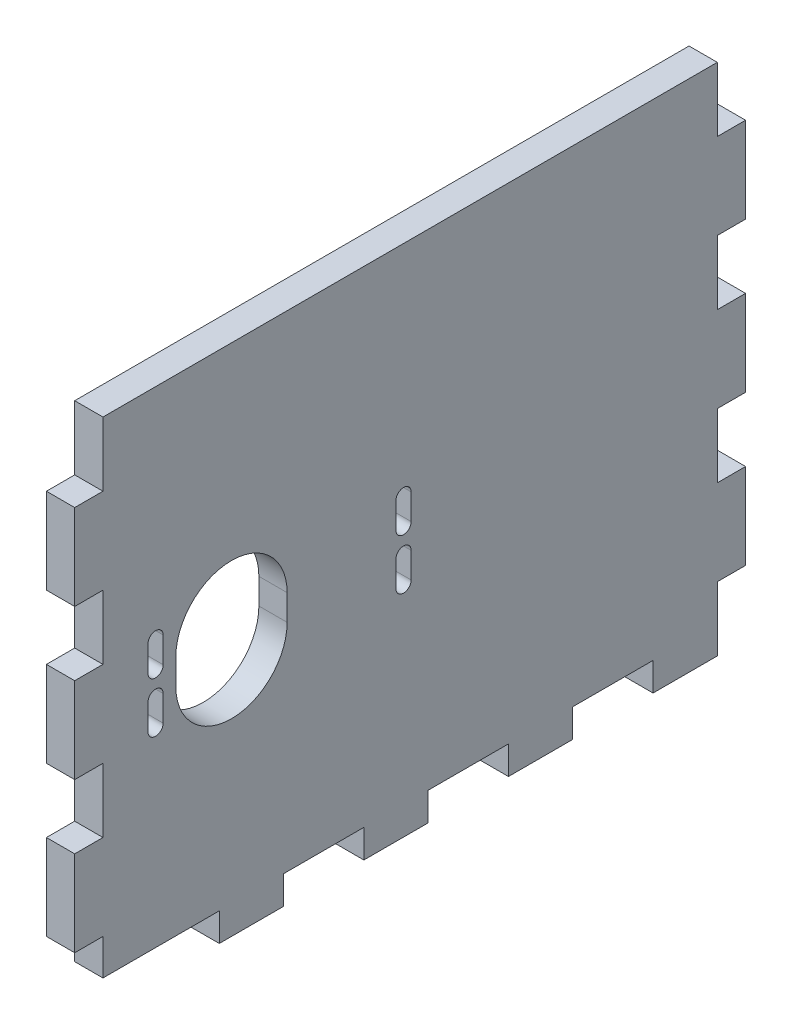
SolidWorks part; units mm, degrees
material "Acrylic (Medium-high impact)"
ref_plane "Front" through (0, 0, 0) normal (0, 0, 1) x (1, 0, 0)
ref_plane "Top" through (0, 0, 0) normal (0, 1, 0) x (1, 0, 0)
ref_plane "Right" through (0, 0, 0) normal (1, 0, 0) x (0, 0, -1)
sketch "Sketch1" plane through (0, 0, 0) normal (0, 0, 1) x (1, 0, 0)
  line L0 (0, 143.002) -> (0, -143.002) construction
  line L1 (-3.302, 133.858) -> (-3.302, -143.002)
  line L2 (-3.302, -143.002) -> (3.302, -143.002)
  line L3 (3.302, 143.002) -> (3.302, -143.002)
  line L4 (3.302, 143.002) -> (-16.256, 143.002)
  line L5 (-5.842, 136.398) -> (-16.256, 136.398)
  line L6 (-16.256, 143.002) -> (-16.256, 136.398)
  line L8 (-28.956, 155.448) -> (16.002, 155.448)
  line L9 (-28.956, 155.448) -> (-28.956, -149.352)
  line L10 (-28.956, -149.352) -> (16.002, -149.352)
  line L11 (16.002, 155.448) -> (16.002, -149.352)
  arc A0 (-3.302, 133.858) -> (-5.842, 136.398) centre (-5.842, 133.858) ccw
  point P2 (0, -143.002)
  point P11 (0, 0)
  dimension "D5" = 2.54
  dimension "D1" = 6.604
  dimension "D2" = 12.954
  dimension "D3" = 6.604
  dimension "D4" = 286.004
  dimension "D6" = 304.8
  dimension "D7" = 6.35
  dimension "D8" = 12.7
  dimension "D9" = 12.7
extrude "Boss-Extrude1" add sketch "Sketch1" along normal blind 5.588
sketch "Sketch2" plane through (16.002, 0, 0) normal (1, 0, 0) x (0, 0, -1)
  line L0 (-5.588, -149.352) -> (-5.588, 155.448) construction
  line L1 (-5.588, -47.752) -> (127, -47.752)
  line L2 (-5.588, -47.752) -> (-5.588, -149.352)
  line L3 (-5.588, -149.352) -> (127, -149.352)
  line L4 (127, -47.752) -> (127, -149.352)
  line L5 (14.4, -101.092) -> (14.4, -96.012)
  line L6 (36.4, -96.012) -> (36.4, -101.092)
  line L7 (8.4, -116.592) -> (8.4, -111.512)
  line L8 (11.4, -116.592) -> (11.4, -111.512)
  line L9 (8.4, -85.592) -> (8.4, -80.512)
  line L10 (11.4, -85.592) -> (11.4, -80.512)
  line L11 (25.4, -96.012) -> (25.4, -101.092) construction
  line L12 (42.4, -116.592) -> (42.4, -111.512)
  line L13 (39.4, -116.592) -> (39.4, -111.512)
  line L14 (39.4, -85.592) -> (39.4, -80.512)
  line L15 (42.4, -85.592) -> (42.4, -80.512)
  line L16 (0, -149.352) -> (0, 155.448) construction
  line L17 (124.206, -60.452) -> (124.206, -77.3853) construction
  line L18 (127, -47.752) -> (121.412, -47.752)
  line L19 (127, -47.752) -> (127, -60.452)
  line L20 (127, -60.452) -> (121.412, -60.452)
  line L21 (121.412, -47.752) -> (121.412, -60.452)
  line L22 (127, -107.0187) -> (121.412, -107.0187)
  line L23 (127, -107.0187) -> (127, -119.7187)
  line L24 (127, -119.7187) -> (121.412, -119.7187)
  line L25 (121.412, -107.0187) -> (121.412, -119.7187)
  line L26 (127, -136.652) -> (121.412, -136.652)
  line L27 (127, -136.652) -> (127, -149.352)
  line L28 (127, -149.352) -> (121.412, -149.352)
  line L29 (121.412, -136.652) -> (121.412, -149.352)
  line L30 (127, -77.3853) -> (121.412, -77.3853)
  line L31 (127, -77.3853) -> (127, -90.0853)
  line L32 (127, -90.0853) -> (121.412, -90.0853)
  line L33 (121.412, -77.3853) -> (121.412, -90.0853)
  line L34 (124.206, -90.0853) -> (124.206, -107.0187) construction
  line L35 (124.206, -119.7187) -> (124.206, -136.652) construction
  line L36 (10.4, -93.552) -> (59.4, -93.552) construction
  line L37 (59.4, -93.552) -> (59.4, -103.552) construction
  line L38 (59.4, -103.552) -> (10.4, -103.552) construction
  line L39 (10.4, -103.552) -> (10.4, -93.552) construction
  line L40 (8.9, -93.552) -> (8.9, -96.092)
  line L41 (11.9, -96.092) -> (11.9, -93.552)
  line L42 (11.9, -93.552) -> (11.9, -91.012)
  line L43 (8.9, -91.012) -> (8.9, -93.552)
  line L44 (8.9, -106.092) -> (8.9, -101.012)
  line L45 (11.9, -101.012) -> (11.9, -106.092)
  line L46 (60.9, -91.012) -> (60.9, -96.092)
  line L47 (57.9, -96.092) -> (57.9, -91.012)
  line L48 (60.9, -106.092) -> (60.9, -101.012)
  line L49 (57.9, -101.012) -> (57.9, -106.092)
  arc A0 (14.4, -101.092) -> (36.4, -101.092) centre (25.4, -101.092) ccw
  arc A1 (36.4, -96.012) -> (14.4, -96.012) centre (25.4, -96.012) ccw
  arc A2 (8.4, -116.592) -> (11.4, -116.592) centre (9.9, -116.592) ccw
  arc A3 (11.4, -111.512) -> (8.4, -111.512) centre (9.9, -111.512) ccw
  arc A4 (8.4, -85.592) -> (11.4, -85.592) centre (9.9, -85.592) ccw
  arc A5 (11.4, -80.512) -> (8.4, -80.512) centre (9.9, -80.512) ccw
  arc A6 (42.4, -116.592) -> (39.4, -116.592) centre (40.9, -116.592) cw
  arc A7 (39.4, -111.512) -> (42.4, -111.512) centre (40.9, -111.512) cw
  arc A8 (42.4, -85.592) -> (39.4, -85.592) centre (40.9, -85.592) cw
  arc A9 (39.4, -80.512) -> (42.4, -80.512) centre (40.9, -80.512) cw
  circle A10 centre (10.4, -93.552) radius 1.5
  circle A11 centre (59.4, -93.552) radius 1.5
  circle A12 centre (10.4, -103.552) radius 1.5
  circle A13 centre (59.4, -103.552) radius 1.5
  arc A14 (8.9, -96.092) -> (11.9, -96.092) centre (10.4, -96.092) ccw
  arc A15 (11.9, -91.012) -> (8.9, -91.012) centre (10.4, -91.012) ccw
  arc A16 (8.9, -101.012) -> (11.9, -101.012) centre (10.4, -101.012) cw
  arc A17 (11.9, -106.092) -> (8.9, -106.092) centre (10.4, -106.092) cw
  arc A18 (60.9, -96.092) -> (57.9, -96.092) centre (59.4, -96.092) cw
  arc A19 (57.9, -91.012) -> (60.9, -91.012) centre (59.4, -91.012) cw
  arc A20 (60.9, -101.012) -> (57.9, -101.012) centre (59.4, -101.012) ccw
  arc A21 (57.9, -106.092) -> (60.9, -106.092) centre (59.4, -106.092) ccw
  point P44 (25.4, -98.552)
  point P47 (-5.588, -98.552)
  point P71 (10.4, -98.552)
  point P72 (14.4, -98.552)
  point P103 (60.9, -93.552)
  point P105 (60.9, -103.552)
  point P106 (11.9, -103.552)
  line M17 (0, -149.352) -> (0, 155.448)
  line M19 (-5.588, 155.448) -> (-5.588, -149.352)
  line M20 (-5.588, -149.352) -> (0, -149.352)
  dimension "D1" = 22
  dimension "D6" = 1.5
  dimension "D10" = 1.5
  dimension "D18" = 3
  dimension "D2" = 5.08
  dimension "D3" = 5.08
  dimension "D4" = 15.5
  dimension "D5" = 15.5
  dimension "D7" = 15.5
  dimension "D8" = 15.5
  dimension "D9" = 5.08
  dimension "D11" = 25.4
  dimension "D12" = 50.8
  dimension "D13" = 101.6
  dimension "D14" = 12.7
  dimension "D15" = 5.588
  dimension "D16" = 10
  dimension "D17" = 49
  dimension "D19" = 5.08
  dimension "D20" = 5.08
  dimension "D21" = 15
extrude "Boss-Extrude2" add sketch "Sketch2" against normal blind 5.588 contours L33 L30 L4 L20 L21 L1 L3 L29 L26 L24 L25 L22 L32 A5 L10 A4 L9 A3 L8 A2 L7 A1 L6 A0 L5 L13 A7 L12 A6 L14 A9 L15 A8 M17 | L1 M19 M20 M17 | L10 A5 L9 A4 | A9 L14 A8 L15 | A7 L13 A6 L12 | L8 A3 L7 A2 region at (16.002, -98.552, -64.1244) region at (16.002, -98.552, 2.794) region at (16.002, -114.052, -9.9) region at (16.002, -83.052, -9.9) region at (16.002, -114.052, -40.9) region at (16.002, -83.052, -40.9)
sketch "Sketch3" plane through (10.414, 0, 0) normal (-1, 0, 0) x (0, 0, 1)
  line L0 (-121.412, -136.652) -> (-121.412, -149.352) construction
  line L1 (-121.412, -143.764) -> (0, -143.764)
  line L2 (-121.412, -143.764) -> (-121.412, -149.352)
  line L3 (-121.412, -149.352) -> (0, -149.352)
  line L4 (0, -143.764) -> (0, -149.352)
  dimension "D1" = 5.588
extrude "Boss-Extrude3" add sketch "Sketch3" along normal up to surface (39.37 mm away) up to face at (-28.956, 3.048, 2.794)
sketch "Sketch4" plane through (0, -149.352, 0) normal (0, -1, 0) x (1, 0, 0)
  line L0 (9.652, -22.987) -> (9.652, -35.687)
  line L1 (16.002, 5.588) -> (9.652, 5.588)
  line L2 (16.002, 5.588) -> (16.002, -7.112)
  line L3 (16.002, -7.112) -> (9.652, -7.112)
  line L4 (9.652, 5.588) -> (9.652, -7.112)
  line L5 (16.002, -22.987) -> (9.652, -22.987)
  line L6 (16.002, -22.987) -> (16.002, -35.687)
  line L7 (16.002, -35.687) -> (9.652, -35.687)
  line L8 (9.652, -51.562) -> (9.652, -64.262)
  line L9 (16.002, -51.562) -> (9.652, -51.562)
  line L10 (16.002, -51.562) -> (16.002, -64.262)
  line L11 (16.002, -64.262) -> (9.652, -64.262)
  line L12 (9.652, -80.137) -> (9.652, -92.837)
  line L13 (16.002, -80.137) -> (9.652, -80.137)
  line L14 (16.002, -80.137) -> (16.002, -92.837)
  line L15 (16.002, -92.837) -> (9.652, -92.837)
  line L16 (9.652, -108.712) -> (9.652, -121.412)
  line L17 (16.002, -108.712) -> (9.652, -108.712)
  line L18 (16.002, -108.712) -> (16.002, -121.412)
  line L19 (16.002, -121.412) -> (9.652, -121.412)
  line L36 (-6.477, 5.588) -> (-6.477, -121.412) construction
  line L37 (-28.956, 5.588) -> (16.002, 5.588) construction
  line L38 (-28.956, -121.412) -> (16.002, -121.412) construction
  line L39 (-22.606, 5.588) -> (-22.606, -121.412)
  line L40 (16.002, 5.588) -> (9.652, 5.588)
  line L41 (16.002, 5.588) -> (16.002, -121.412)
  line L42 (16.002, -121.412) -> (9.652, -121.412)
  line L43 (9.652, 5.588) -> (9.652, -121.412)
  line L44 (-28.956, -121.412) -> (-22.606, -121.412)
  line L45 (-28.956, 5.588) -> (-28.956, -121.412)
  line L46 (-28.956, 5.588) -> (-22.606, 5.588)
  line L47 (-28.956, -121.412) -> (-22.606, -121.412)
  line L48 (-28.956, -107.95) -> (-28.956, -121.412)
  line L49 (-28.956, -107.95) -> (-22.606, -107.95)
  line L50 (-22.606, -107.95) -> (-22.606, -121.412)
  line L51 (-28.956, -106.3625) -> (-22.606, -106.3625)
  line L52 (-28.956, -93.6625) -> (-28.956, -106.3625)
  line L53 (-28.956, -93.6625) -> (-22.606, -93.6625)
  line L54 (-22.606, -93.6625) -> (-22.606, -106.3625)
  line L55 (-28.956, -92.075) -> (-22.606, -92.075)
  line L56 (-28.956, -79.375) -> (-28.956, -92.075)
  line L57 (-28.956, -79.375) -> (-22.606, -79.375)
  line L58 (-22.606, -79.375) -> (-22.606, -92.075)
  line L59 (-28.956, -77.7875) -> (-22.606, -77.7875)
  line L60 (-28.956, -65.0875) -> (-28.956, -77.7875)
  line L61 (-28.956, -65.0875) -> (-22.606, -65.0875)
  line L62 (-22.606, -65.0875) -> (-22.606, -77.7875)
  line L63 (-28.956, -121.412) -> (-22.606, -121.412)
  line L64 (-28.956, -108.712) -> (-28.956, -121.412)
  line L65 (-28.956, -108.712) -> (-22.606, -108.712)
  line L66 (-22.606, -108.712) -> (-22.606, -121.412)
  line L67 (-28.956, -92.837) -> (-22.606, -92.837)
  line L68 (-28.956, -80.137) -> (-28.956, -92.837)
  line L69 (-28.956, -80.137) -> (-22.606, -80.137)
  line L70 (-22.606, -80.137) -> (-22.606, -92.837)
  line L71 (-28.956, -64.262) -> (-22.606, -64.262)
  line L72 (-28.956, -51.562) -> (-28.956, -64.262)
  line L73 (-28.956, -51.562) -> (-22.606, -51.562)
  line L74 (-22.606, -51.562) -> (-22.606, -64.262)
  line L75 (-28.956, -35.687) -> (-22.606, -35.687)
  line L76 (-28.956, -22.987) -> (-28.956, -35.687)
  line L77 (-28.956, -22.987) -> (-22.606, -22.987)
  line L78 (-22.606, 5.588) -> (-22.606, -7.112)
  line L79 (-28.956, -7.112) -> (-22.606, -7.112)
  line L80 (-28.956, 5.588) -> (-28.956, -7.112)
  line L81 (-28.956, 5.588) -> (-22.606, 5.588)
  line L82 (-22.606, -22.987) -> (-22.606, -35.687)
  line L83 (-16.129, 2.794) -> (-22.606, 2.794) construction
  line L85 (-28.956, 5.588) -> (-22.606, 5.588)
  line L86 (-28.956, 5.588) -> (-28.956, 0)
  line L87 (-28.956, 0) -> (-22.606, 0)
  line L88 (-22.606, 5.588) -> (-22.606, 0)
  line L92 (9.652, 5.588) -> (9.652, 0)
  line L93 (9.652, 5.588) -> (16.002, 5.588)
  line L94 (16.002, 5.588) -> (16.002, 0)
  line L95 (9.652, 0) -> (16.002, 0)
  line L96 (-28.956, 5.588) -> (16.002, 5.588)
  line L97 (-28.956, 5.588) -> (-28.956, 0)
  line L98 (-28.956, 0) -> (16.002, 0)
  line L99 (16.002, 5.588) -> (16.002, 0)
  line L100 (-9.652, 5.588) -> (-9.652, 0)
  line L101 (-9.652, 0) -> (-3.302, 0)
  line L102 (-3.302, 5.588) -> (-3.302, 0)
  line L103 (-9.652, 5.588) -> (-3.302, 5.588)
  line L104 (-9.779, 0) -> (-16.129, 0)
  line L105 (-9.779, 0) -> (-9.779, 5.588)
  line L106 (-9.779, 5.588) -> (-16.129, 5.588)
  line L107 (-16.129, 0) -> (-16.129, 5.588)
  line L108 (-9.779, 2.794) -> (-3.302, 2.794) construction
  line L109 (-3.302, 5.588) -> (-3.302, 0) construction
  line L111 (-28.956, 5.588) -> (16.002, 5.588)
  line L112 (-28.956, 5.588) -> (-28.956, 0)
  line L113 (-28.956, 0) -> (16.002, 0)
  line L114 (16.002, 5.588) -> (16.002, 0)
  line M38 (16.002, -121.412) -> (16.002, 5.588)
  line M39 (16.002, 5.588) -> (-28.956, 5.588)
  dimension "D1" = 6.35
  dimension "D2" = 12.7
  dimension "D4" = 5.588
  dimension "D5" = 6.35
  dimension "D7" = 6.35
  dimension "D3" = 5
  dimension "D6" = 3
sketch "Sketch6" plane through (0, 0, 5.588) normal (0, 0, 1) x (1, 0, 0)
  line L1 (16.002, -60.452) -> (10.414, -60.452)
  line L2 (16.002, -60.452) -> (16.002, -77.3853)
  line L3 (16.002, -77.3853) -> (10.414, -77.3853)
  line L4 (10.414, -60.452) -> (10.414, -77.3853)
  line L5 (16.002, -90.0853) -> (10.414, -90.0853)
  line L6 (16.002, -90.0853) -> (16.002, -107.0187)
  line L7 (16.002, -107.0187) -> (10.414, -107.0187)
  line L8 (10.414, -90.0853) -> (10.414, -107.0187)
  line L9 (16.002, -119.7187) -> (10.414, -119.7187)
  line L10 (16.002, -119.7187) -> (16.002, -136.652)
  line L11 (16.002, -136.652) -> (10.414, -136.652)
  line L12 (10.414, -119.7187) -> (10.414, -136.652)
  line L13 (-28.956, -149.352) -> (16.002, -149.352) construction
  line L14 (16.002, -47.752) -> (10.414, -47.752)
  line L15 (16.002, -47.752) -> (16.002, -149.352)
  line L16 (16.002, -149.352) -> (10.414, -149.352)
  line L17 (10.414, -47.752) -> (10.414, -149.352)
  line M1 (16.002, -149.352) -> (16.002, 155.448)
  line M4 (-28.956, -149.352) -> (16.002, -149.352)
sketch "Sketch7" plane through (16.002, 0, 0) normal (1, 0, 0) x (0, 0, -1)
  line L1 (-5.588, 180.723) -> (327.0227, 180.723)
  line L2 (-5.588, 180.723) -> (-5.588, -143.002)
  line L3 (-5.588, -143.002) -> (327.0227, -143.002)
  line L4 (327.0227, 180.723) -> (327.0227, -143.002)
  line L5 (-5.588, -149.352) -> (-5.588, 155.448) construction
  line L6 (121.412, -143.002) -> (0, -143.002) construction
  point P10 (160.7174, -143.002)
extrude "Cut-Extrude1" [suppressed] cut sketch "Sketch7" against normal through all
extrude "Cut-Extrude2" [suppressed] cut sketch "Sketch4" against normal blind 6.35
sketch "Sketch8" plane through (0, 0, 5.588) normal (0, 0, 1) x (1, 0, 0)
  line L0 (-28.956, -149.352) -> (16.002, -149.352) construction
  line L1 (10.414, -149.352) -> (-54.2235, -149.352)
  line L2 (10.414, -149.352) -> (10.414, 165.6994)
  line L3 (10.414, 165.6994) -> (-54.2235, 165.6994)
  line L4 (-54.2235, -149.352) -> (-54.2235, 165.6994)
  line L5 (10.414, -60.452) -> (10.414, -77.3853) construction
  line L7 (16.002, -47.752) -> (10.414, -47.752)
  line L8 (16.002, -47.752) -> (16.002, 165.6994)
  line L9 (16.002, 165.6994) -> (10.414, 165.6994)
  line L10 (10.414, -47.752) -> (10.414, 165.6994)
  line M6 (16.002, 155.448) -> (-28.956, 155.448)
  line M7 (-28.956, 155.448) -> (-28.956, -149.352)
  line M8 (-28.956, -149.352) -> (16.002, -149.352)
  line M9 (-16.256, 143.002) -> (3.302, 143.002)
  line M10 (3.302, 143.002) -> (3.302, -143.002)
  line M11 (3.302, -143.002) -> (-3.302, -143.002)
  line M12 (-3.302, -143.002) -> (-3.302, 133.858)
  arc M13 (-3.302, 133.858) -> (-5.842, 136.398) centre (-5.842, 133.858) ccw
  line M14 (-5.842, 136.398) -> (-16.256, 136.398)
  line M15 (-16.256, 136.398) -> (-16.256, 143.002)
extrude "Cut-Extrude4" cut sketch "Sketch8" against normal through all and the other way through all contours L2 M8 M6 M7 M15 M9 M10 M11 M12 M13 M14 | L4 L1 L2 L3 M7 M6 | L10 L7 L8 L9 region at (-11.0142, 2.4378, 5.588) region at (-40.0303, 15.5274, 5.588)
extrude "Cut-Extrude5" cut sketch "Sketch6" against normal blind 5.588 contours L14 L17 L1 M1 | L3 L17 L5 M1 | L7 L17 L9 M1 | L11 L17 M4 M1 region at (13.208, -54.102, 5.588) region at (13.208, -83.7353, 5.588) region at (13.208, -113.3687, 5.588) region at (13.208, -143.002, 5.588)
extrude "Cut-Extrude6" cut sketch "Sketch4<3>" against normal blind 5.588 contours L15 L43 L17 M38 | L11 L43 L13 M38 | L7 L43 L9 M38 | L3 L43 L5 M38 | L4 L95 L41 M39 | L95 L43 L3 M38 region at (12.827, -149.352, -15.0495) region at (12.827, -149.352, -43.6245) region at (12.827, -149.352, -3.556) region at (12.827, -149.352, 2.794) region at (12.827, -149.352, -72.1995) region at (12.827, -149.352, -100.7745)
sketch "Sketch4<3>" plane through (0, -149.352, 0) normal (0, -1, 0) x (1, 0, 0) same geometry as "Sketch4"
